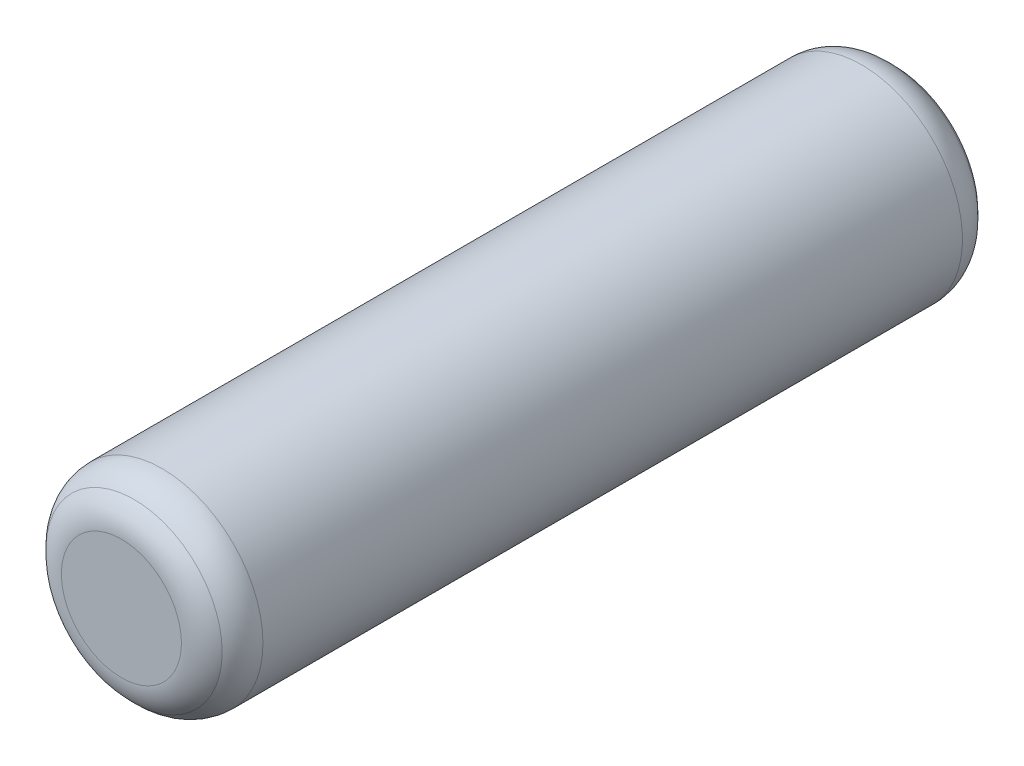
SolidWorks part; units mm, degrees
ref_plane "Front Plane" through (0, 0, 0) normal (0, 0, 1) x (1, 0, 0)
ref_plane "Top Plane" through (0, 0, 0) normal (0, 1, 0) x (1, 0, 0)
ref_plane "Right Plane" through (0, 0, 0) normal (1, 0, 0) x (0, 0, -1)
sketch "Sketch4" plane through (0, 0, 0) normal (0, 0, 1) x (1, 0, 0)
  circle A0 centre (0, 0) radius 2
  dimension "D1" = 4
extrude "Boss-Extrude2" add sketch "Sketch4" along normal blind 15 contours A0
sketch "Sketch5" plane through (0, 0, 15) normal (0, 0, 1) x (1, 0, 0)
  circle A0 centre (0, 0) radius 1.75
  dimension "D1" = 3.5
extrude "Boss-Extrude3" add sketch "Sketch5" along normal blind 0.25
fillet "Fillet3" radius 0.75 2 edges at (2, 0, 15) (1.75, 0, 15.25)
sketch "Sketch6" plane through (0, 0, 0) normal (0, 0, -1) x (-1, 0, 0)
  circle A0 centre (0, 0) radius 1.75
  dimension "D1" = 3.5
extrude "Boss-Extrude4" add sketch "Sketch6" along normal blind 0.25
fillet "Fillet4" radius 0.75 2 edges at (2, 0, 0) (-1.75, 0, -0.25)
